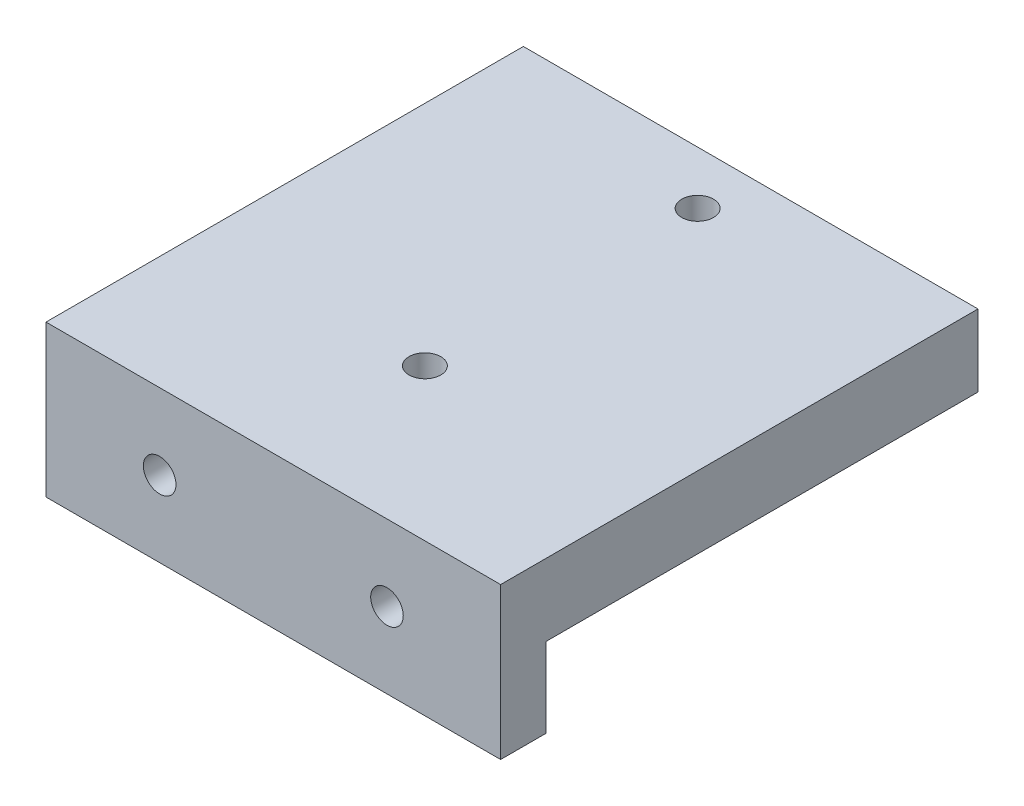
SolidWorks part; units mm, degrees
ref_plane "Front Plane" through (0, 0, 0) normal (0, 0, 1) x (1, 0, 0)
ref_plane "Top Plane" through (0, 0, 0) normal (0, 1, 0) x (1, 0, 0)
ref_plane "Right Plane" through (0, 0, 0) normal (1, 0, 0) x (0, 0, -1)
ref_plane "PL_Zp14" through (0, 14, 0) normal (0, 1, 0) x (1, 0, 0)
sketch "SK_Top" plane through (0, 14, 0) normal (0, 1, 0) x (1, 0, 0)
  line L1 (-30, 25) -> (30, 25)
  line L2 (-30, 25) -> (-30, -38)
  line L3 (-30, -38) -> (30, -38)
  line L4 (30, 25) -> (30, -38)
  dimension "D1" = 63
  dimension "D2" = 60
  dimension "D3" = 25
  dimension "D4" = 30
extrude "EX_Top" add sketch "SK_Top" along normal blind 9.5
ref_plane "PL_Zp3_5" through (0, 3.5, 0) normal (0, 1, 0) x (1, 0, 0)
sketch "SK_BackWall" plane through (0, 3.5, 0) normal (0, 1, 0) x (1, 0, 0)
  line L1 (-30, -32) -> (30, -32)
  line L2 (-30, -32) -> (-30, -38)
  line L3 (-30, -38) -> (30, -38)
  line L4 (30, -32) -> (30, -38)
  dimension "D1" = 6
  dimension "D2" = 60
  dimension "D3" = 32
  dimension "D4" = 30
extrude "EX_BackWall" add sketch "SK_BackWall" along normal blind 10.5
ref_plane "PL_Xp38" through (0, 0, 38) normal (0, 0, 1) x (1, 0, 0)
sketch "SK_RailBolts" plane through (0, 0, 38) normal (0, 0, 1) x (1, 0, 0)
  circle A0 centre (15, 13.5) radius 2.15
  circle A1 centre (-15, 13.5) radius 2.15
  dimension "D3" = 4.3
  dimension "D6" = 4.3
  dimension "D1" = 15
  dimension "D2" = 13.5
  dimension "D4" = 15
  dimension "D5" = 13.5
extrude "CUT_RailBolts" cut sketch "SK_RailBolts" against normal blind 8
sketch "SK_GuidePins" plane through (0, 14, 0) normal (0, 1, 0) x (1, 0, 0)
  circle A0 centre (0, -18) radius 2.1
  circle A1 centre (0, 18) radius 2.1
  dimension "D2" = 4.2
  dimension "D4" = 4.2
  dimension "D1" = 18
  dimension "D3" = 18
extrude "CUT_GuidePins" cut sketch "SK_GuidePins" along normal blind 9.5
sketch "SK_SpringSeats" plane through (0, 14, 0) normal (0, 1, 0) x (1, 0, 0)
  circle A0 centre (18, 0) radius 5
  circle A1 centre (-18, 0) radius 5
  dimension "D2" = 10
  dimension "D4" = 10
  dimension "D1" = 18
  dimension "D3" = 18
extrude "CUT_SpringSeats" cut sketch "SK_SpringSeats" along normal blind 5
ref_axis "AX_X" through (0, 0, -28.15) along (0, 0, 1)
ref_axis "AX_Y" through (33, 0, 0) along (-1, 0, 0)
ref_axis "AX_Z" through (0, 24.5, 0) along (0, -1, 0)
